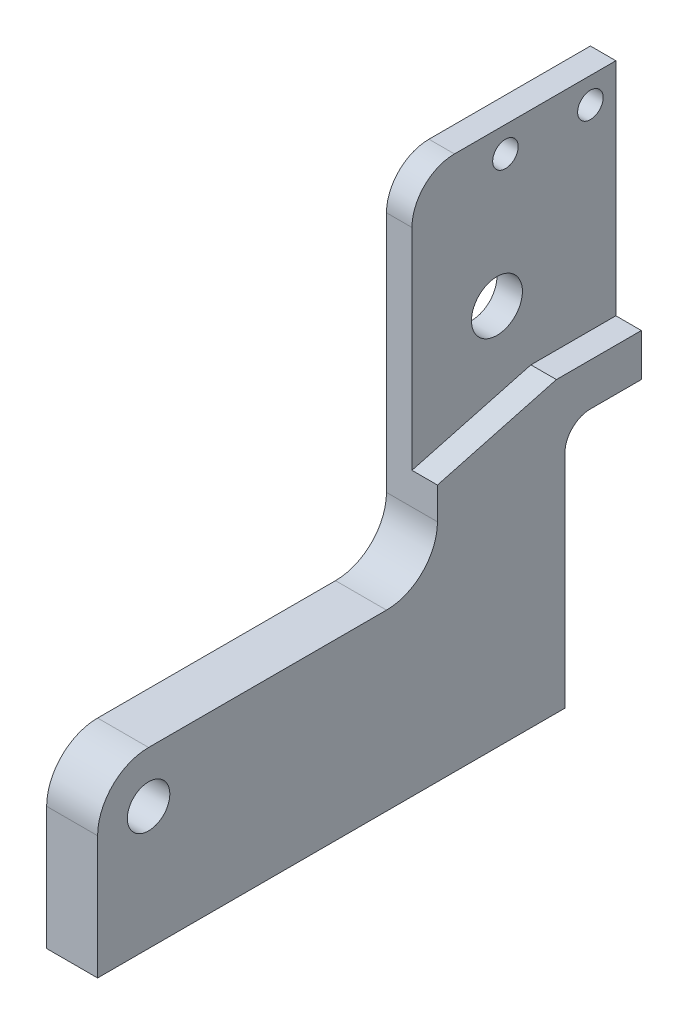
SolidWorks part; units mm, degrees
material "1060 Alloy"
ref_plane "Front Plane" through (0, 0, 0) normal (0, 0, 1) x (1, 0, 0)
ref_plane "Top Plane" through (0, 0, 0) normal (0, 1, 0) x (1, 0, 0)
ref_plane "Right Plane" through (0, 0, 0) normal (1, 0, 0) x (0, 0, -1)
sketch "Sketch1" plane through (0, 0, 0) normal (1, 0, 0) x (0, 0, -1)
  line L1 (0, 0) -> (64, 0)
  line L2 (0, 0) -> (0, 60)
  line L3 (0, 60) -> (64, 60)
  line L4 (64, 0) -> (64, 60)
  circle A0 centre (6, 14.5) radius 2.5
  circle A1 centre (50, 42) radius 3
  dimension "D1" = 6
  dimension "D2" = 5
  dimension "D3" = 14.5
  dimension "D4" = 6
  dimension "D5" = 42
  dimension "D6" = 50
  dimension "D7" = 64
  dimension "D8" = 60
extrude "Boss-Extrude1" add sketch "Sketch1" along normal blind 6
sketch "Sketch3" plane through (6, 0, 0) normal (1, 0, 0) x (0, 0, -1)
  line L1 (0, 60) -> (0, 0) construction
  line L57 (64, 0) -> (55, 0)
  line L58 (64, 0) -> (64, 29)
  line L59 (64, 29) -> (55, 29)
  line L60 (55, 0) -> (55, 29)
  dimension "D1" = 29
  dimension "D2" = 55
extrude "Cut-Extrude2" cut sketch "Sketch3" against normal up to next
fillet "Fillet2" radius 3 1 edges at (3, 29, -55)
hole_wizard "Tap Drill for M3 Tap1" positions "Sketch5" profile "Sketch4" hole size "M3" standard "ISO"
sketch "Sketch5" plane through (0, 0, 0) normal (0, -1, 0) x (-1, 0, 0)
  line L0 (0, 0) -> (0, 55) construction
  line L1 (-6, 0) -> (0, 0) construction
  point P0 (-3, 48)
  point P2 (-3, 12)
  dimension "D1" = 3
  dimension "D2" = 12
  dimension "D3" = 36
sketch "Sketch4" plane through (3, 0, -48) normal (1, 0, 0) x (0, 0, -1)
  line L0 (0, 0) -> (0, 10.7511)
  line L1 (0, 10.7511) -> (1.25, 10)
  line L2 (1.25, 10) -> (1.25, 0)
  line L5 (1.25, 0) -> (0, 0)
  line L10 (0, 10.7511) -> (-1.25, 10) construction
  line L11 (0, -6.35) -> (0, 107.95) construction
  dimension "Hole Dia." = 2.5
  dimension "Hole Depth" = 10
  dimension "Drill Angle" = 118
sketch "Sketch9" plane through (6, 0, 0) normal (1, 0, 0) x (0, 0, -1)
  line L0 (6, 20.5) -> (34, 20.5)
  line L19 (40, 60) -> (40, 26.5)
  line L21 (0, 60) -> (0, 0) construction
  line L22 (40, 60) -> (0, 60)
  line L23 (0, 60) -> (0, 14.5)
  line L24 (0, 60) -> (0, 0) construction
  line L25 (64, 60) -> (0, 60) construction
  arc A0 (40, 26.5) -> (34, 20.5) centre (34, 26.5) cw
  arc A12 (0, 14.5) -> (6, 20.5) centre (6, 14.5) cw
  circle A16 centre (6, 14.5) radius 2.5 construction
  dimension "D1" = 40
extrude "Cut-Extrude3" cut sketch "Sketch9" against normal blind 8
sketch "Sketch13" plane through (6, 0, 0) normal (1, 0, 0) x (0, 0, -1)
  line L0 (64, 29) -> (64, 60) construction
  line L1 (54, 34) -> (64, 34)
  line L2 (64, 60) -> (40, 60) construction
  line L3 (64, 60) -> (40, 60)
  line L4 (64, 34) -> (64, 60)
  line L5 (40, 26.5) -> (40, 60) construction
  line L11 (40, 60) -> (40, 30.2487)
  line L15 (40, 30.2487) -> (54, 34)
  dimension "D1" = 10
  dimension "D2" = 75
  dimension "D3" = 26
extrude "Cut-Extrude4" cut sketch "Sketch13" against normal blind 3
fillet "Fillet3" radius 5 1 edges at (1.5, 60, -40)
sketch "Sketch14" plane through (3, 0, 0) normal (1, 0, 0) x (0, 0, -1)
  line L0 (64, 34) -> (64, 60) construction
  line L1 (64, 60) -> (45, 60) construction
  circle A0 centre (61, 57) radius 1.5
  circle A1 centre (51, 57) radius 1.5
  dimension "D1" = 3
  dimension "D2" = 10
  dimension "D3" = 3
  dimension "D4" = 3
extrude "Cut-Extrude5" cut sketch "Sketch14" against normal up to next
